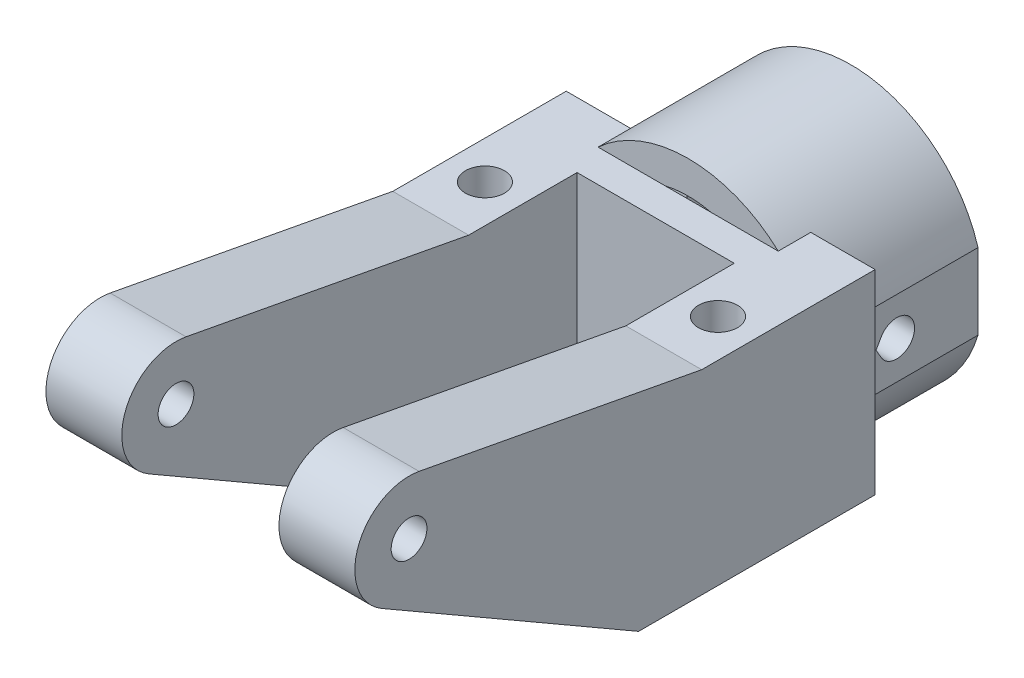
SolidWorks part; units mm, degrees
ref_plane "正面(Front)" through (0, 0, 0) normal (0, 0, 1) x (1, 0, 0)
ref_plane "平面(Top)" through (0, 0, 0) normal (0, 1, 0) x (1, 0, 0)
ref_plane "右側面(Right)" through (0, 0, 0) normal (1, 0, 0) x (0, 0, -1)
sketch "ｽｹｯﾁ1" plane through (0, 0, 0) normal (0, 0, 1) x (1, 0, 0)
  circle A0 centre (0, 0) radius 6.325
  dimension "D1" = 12.65
extrude "ﾎﾞｽ - 押し出し1" add sketch "ｽｹｯﾁ1" along normal blind 15
sketch "ｽｹｯﾁ2" plane through (0, 0, 15) normal (0, 0, 1) x (1, 0, 0)
  line L1 (-14.25, 9) -> (14.25, 9)
  line L2 (-14.25, 9) -> (-14.25, -9)
  line L3 (-14.25, -9) -> (14.25, -9)
  line L4 (14.25, 9) -> (14.25, -9)
  line L5 (-14.25, 9) -> (14.25, -9) construction
  line L6 (-14.25, -9) -> (14.25, 9) construction
  point P0 (0, 0)
  dimension "D1" = 18
  dimension "D2" = 28.5
extrude "ﾎﾞｽ - 押し出し2" add sketch "ｽｹｯﾁ2" along normal blind 3
sketch "ｽｹｯﾁ4" plane through (0, 0, 0) normal (1, 0, 0) x (0, 0, -1)
  line L0 (-18, 9) -> (-42.311, 9) construction
  line L2 (-54.0741, 13.9135) -> (-28, 9)
  line L3 (-28, 9) -> (-18, 9)
  line L5 (-18, 9) -> (-18, -9)
  line L6 (-18, -9) -> (-18, 9) construction
  line L7 (-56.6248, 4.2713) -> (-18, -9)
  line L8 (-18, -9) -> (-15, -9) construction
  arc A0 (-54.0741, 13.9135) -> (-56.6248, 4.2713) centre (-55, 9) ccw
  circle A1 centre (-55, 9) radius 1.65
  dimension "D2" = 5
  dimension "D1" = 3.3
  dimension "D3" = 37
  dimension "D4" = 10
extrude "ﾎﾞｽ - 押し出し3" add sketch "ｽｹｯﾁ4" against normal blind 7 from surface starting at face at (14.25, 0, 16.5)
extrude "ﾎﾞｽ - 押し出し4" add sketch "ｽｹｯﾁ4<2>" along normal blind 7 from surface starting at face at (-14.25, 0, 16.5)
sketch "ｽｹｯﾁ4<2>" plane through (0, 0, 0) normal (1, 0, 0) x (0, 0, -1) same geometry as "ｽｹｯﾁ4"
sketch "ｽｹｯﾁ5" plane through (-14.25, 0, 0) normal (-1, 0, 0) x (0, 0, 1)
  line L0 (18, -9) -> (33.8231, -9)
  line L1 (33.8231, -9) -> (57.5, 4.6699)
  line L2 (56.6248, 4.2713) -> (18, -9) construction
  line L3 (56.6248, 4.2713) -> (18, -9)
  arc A0 (56.6248, 4.2713) -> (54.0741, 13.9135) centre (55, 9) ccw construction
  arc A1 (56.6248, 4.2713) -> (57.5, 4.6699) centre (55, 9) ccw
  dimension "D1" = 30
extrude "ﾎﾞｽ - 押し出し5" add sketch "ｽｹｯﾁ5" against normal blind 7
mirror "ﾐﾗｰ1" about plane through (0, 0, 0) normal (1, 0, 0) of "ﾎﾞｽ - 押し出し5"
sketch "ｽｹｯﾁ7" plane through (0, 9, 0) normal (0, 1, 0) x (1, 0, 0)
  line L0 (10.75, -28) -> (10.75, -12.373) construction
  line L1 (7.25, -28) -> (14.25, -28) construction
  line L2 (7.25, -18) -> (-7.25, -18) construction
  line L3 (0, 0) -> (0, -40.3817) construction
  circle A0 centre (10.75, -23) radius 1.8
  circle A1 centre (-10.75, -23) radius 1.8
  dimension "D1" = 3.6
  dimension "D2" = 5
extrude "ｶｯﾄ - 押し出し1" cut sketch "ｽｹｯﾁ7" against normal through all
chamfer "面取り1" [suppressed] distance 1 angle 45
chamfer "面取り2" [suppressed] distance 1 angle 45
sketch "ｽｹｯﾁ8" [suppressed] plane through (0, 0, 0) normal (1, 0, 0) x (0, 0, -1)
  line L0 (0, 0) -> (-14.2374, 0) construction
  line L1 (0, -5.325) -> (0, 5.325) construction
  circle A0 centre (-7.5, 0) radius 1.65
  dimension "D1" = 7.5
  dimension "D2" = 3.3
extrude "ｶｯﾄ - 押し出し2" [suppressed] cut sketch "ｽｹｯﾁ8" against normal through all both and the other way through all
sketch "ｽｹｯﾁ9" plane through (14.25, 0, 0) normal (1, 0, 0) x (0, 0, -1)
  line L0 (-15, 12.9934) -> (-15, -12.9274)
  line L1 (-15, -9) -> (-15, 9) construction
  point P2 (-9.9861, 12.9934)
extrude "ｶｯﾄ - 押し出し3" cut sketch "ｽｹｯﾁ9" against normal through all and the other way through all
sketch "ｽｹｯﾁ10" plane through (0, 0, 15) normal (0, 0, -1) x (-1, 0, 0)
  circle A0 centre (0, 0) radius 9.25
  circle A1 centre (0, 0) radius 12.25
  dimension "D1" = 18.5
  dimension "D2" = 3
extrude "ﾎﾞｽ - 押し出し6" add sketch "ｽｹｯﾁ10" along normal blind 15
sketch "ｽｹｯﾁ11" plane through (0, 0, 15) normal (0, 0, -1) x (-1, 0, 0)
  line L3 (8.3104, -9) -> (14.25, -9)
  line L4 (14.25, -9) -> (14.25, 9)
  line L5 (14.25, 9) -> (8.3104, 9)
  line L6 (8.3104, -9) -> (14.25, -9)
  line L7 (14.25, -9) -> (14.25, 9)
  line L8 (14.25, 9) -> (8.3104, 9)
  line L9 (-8.3104, 9) -> (-14.25, 9)
  line L10 (-14.25, 9) -> (-14.25, -9)
  line L11 (-14.25, -9) -> (-8.3104, -9)
  line L12 (-8.3104, 9) -> (-14.25, 9)
  line L13 (-14.25, 9) -> (-14.25, -9)
  line L14 (-14.25, -9) -> (-8.3104, -9)
  arc A1 (8.3104, -9) -> (8.3104, 9) centre (0, 0) ccw
  arc A2 (8.3104, -9) -> (8.3104, 9) centre (0, 0) ccw
  arc A3 (-8.3104, 9) -> (-8.3104, -9) centre (0, 0) ccw
  arc A4 (-8.3104, 9) -> (-8.3104, -9) centre (0, 0) ccw
  dimension "D1" = 0
  dimension "D2" = 0
extrude "ﾎﾞｽ - 押し出し7" add sketch "ｽｹｯﾁ11" along normal blind 3
sketch "ｽｹｯﾁ12" plane through (0, 0, 0) normal (1, 0, 0) x (0, 0, -1)
  line L0 (-15, 12.25) -> (-15, 9) construction
  line L1 (0, 0) -> (-14.3399, 0) construction
  line L2 (-9.4053, 0) -> (-8.9289, 0.825)
  line L3 (-9.4053, 0) -> (-8.9289, -0.825)
  arc A0 (-8.9289, -0.825) -> (-8.9289, 0.825) centre (-7.5, 0) ccw
  point P9 (-9.5998, 0)
  dimension "D1" = 3.3
  dimension "D2" = 7.5
  dimension "D3" = 60
extrude "ｶｯﾄ - 押し出し4" cut sketch "ｽｹｯﾁ12" against normal through all both and the other way through all
sketch "ｽｹｯﾁ13" plane through (0, 0, 0) normal (0, 0, -1) x (-1, 0, 0)
  line L0 (0, 0) -> (0, 16.0887) construction
  line L1 (11.7394, -3.5) -> (19.1232, -3.5)
  line L2 (11.7394, -3.5) -> (11.7394, 3.5)
  line L3 (11.7394, 3.5) -> (19.1232, 3.5)
  line L4 (19.1232, -3.5) -> (19.1232, 3.5)
  line L5 (-11.7394, 3.5) -> (-19.1232, 3.5)
  line L6 (-19.1232, -3.5) -> (-19.1232, 3.5)
  line L7 (-11.7394, -3.5) -> (-19.1232, -3.5)
  line L8 (-11.7394, -3.5) -> (-11.7394, 3.5)
  arc A0 (8.3104, -9) -> (8.3104, 9) centre (0, 0) ccw construction
  circle A1 centre (0, 0) radius 12.25 construction
  dimension "D1" = 7
extrude "ｶｯﾄ - 押し出し5" cut sketch "ｽｹｯﾁ13" against normal up to surface (12 mm away) up to face at (12.2651, 0, 12)
sketch "ｽｹｯﾁ14" plane through (0, 0, 0) normal (0, 0, -1) x (-1, 0, 0)
  line L0 (4, -11.5785) -> (-4, -11.5785)
  arc A0 (-11.7394, -3.5) -> (11.7394, -3.5) centre (0, 0) ccw construction
  dimension "D1" = 8
extrude "ｶｯﾄ - 押し出し6" cut sketch "ｽｹｯﾁ14" against normal through all and the other way through all
chamfer "面取り3" distance 1 angle 80 1 edges at (0, -11.5785, 0) first distance on face at (-9.25, 0, 0)
